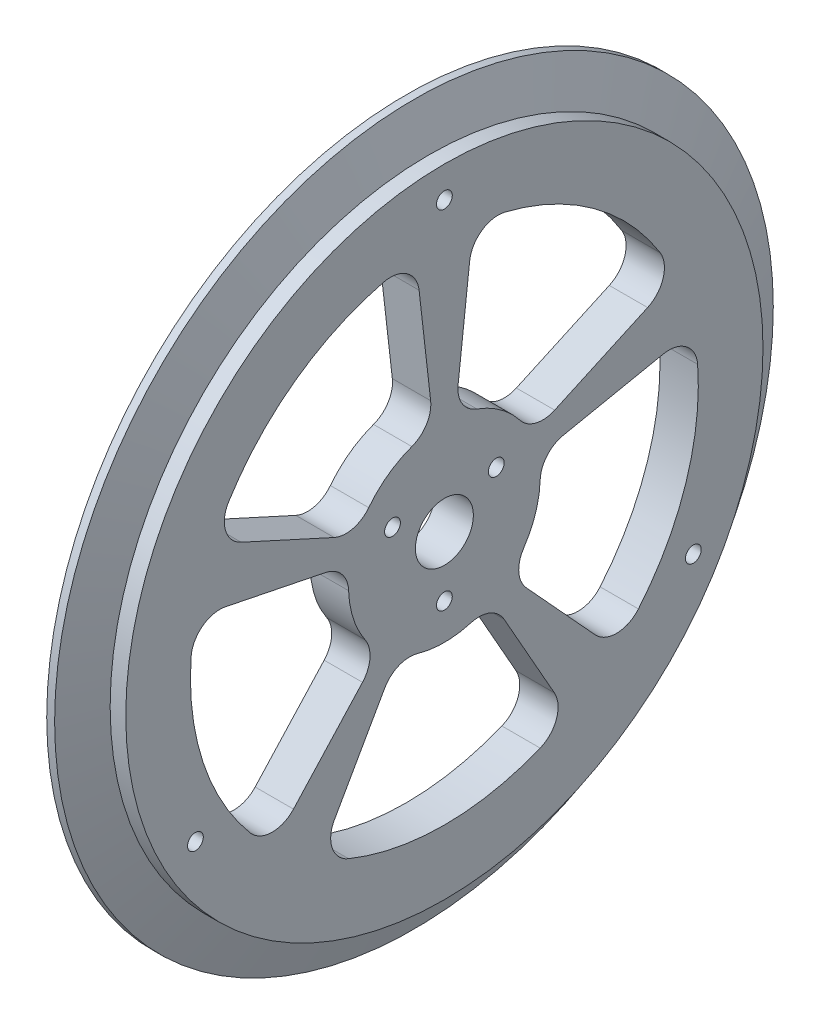
SolidWorks part; units mm, degrees
ref_plane "Front Plane" through (0, 0, 0) normal (0, 0, 1) x (1, 0, 0)
ref_plane "Top Plane" through (0, 0, 0) normal (0, 1, 0) x (1, 0, 0)
ref_plane "Right Plane" through (0, 0, 0) normal (1, 0, 0) x (0, 0, -1)
sketch "Sketch3" plane through (0, 0, 0) normal (0, 0, 1) x (1, 0, 0)
  line L1 (0, 0) -> (8, 0)
  line L2 (0, 0) -> (0, 75)
  line L3 (0, 75) -> (1.65, 75)
  line L5 (8, 120) -> (8, 104.2471) construction
  line L6 (8, 66.5) -> (4.7437, 66.5)
  line L8 (1.65, 75) -> (4.7437, 66.5)
  line L9 (8, 66.5) -> (8, 0)
  point P11 (8, 66.5)
  dimension "D1" = 8
  dimension "D2" = 75
  dimension "D3" = 6.35
  dimension "D4" = 20
  dimension "D5" = 8.5
  dimension "D6" = 1.65
revolve "Revolve1" add sketch "Sketch3" angle 360 about L1
ref_plane "Plane1" through (0, -36, 0) normal (0, 1, 0) x (1, 0, 0)
sketch "Sketch6" plane through (0, -36, 0) normal (0, 1, 0) x (1, 0, 0)
  line L0 (0, 75) -> (0, -75) construction
  line L1 (0, 2.5) -> (2, 2.5)
  line L2 (0, 2.5) -> (0, -2.5)
  line L3 (0, -2.5) -> (2, -2.5)
  line L4 (2, 2.5) -> (2, -2.5)
  line L5 (0, 0) -> (6.7273, 0) construction
  dimension "D1" = 5
  dimension "D2" = 2
extrude "Cut-Extrude2" [suppressed] cut sketch "Sketch6" against normal blind 65.4
sketch "Sketch5" plane through (0, 0, 0) normal (1, 0, 0) x (0, 0, -1)
  circle A0 centre (0, 0) radius 6.05
  dimension "D1" = 12.1
extrude "Cut-Extrude1" cut sketch "Sketch5" along normal through all
sketch "Sketch7" plane through (8, 0, 0) normal (1, 0, 0) x (0, 0, -1)
  line L0 (0, 0) -> (96.1964, -55.539) construction
  line L1 (0, 0) -> (0, 79.1103) construction
  line L2 (0, 0) -> (-91.2375, -52.676) construction
  line L3 (0, 0) -> (43.1357, 24.9044) construction
  line L4 (0, 0) -> (-44.6886, 25.801) construction
  line L5 (0, 0) -> (0, -35.7972) construction
  circle A0 centre (0, 0) radius 60 construction
  circle A1 centre (0, 60) radius 1.65
  circle A2 centre (51.9615, -30) radius 1.65
  circle A3 centre (-51.9615, -30) radius 1.65
  circle A4 centre (0, 0) radius 12.5 construction
  circle A5 centre (10.8253, 6.25) radius 1.65
  circle A6 centre (0, -12.5) radius 1.65
  circle A7 centre (-10.8253, 6.25) radius 1.65
  dimension "D3" = 120
  dimension "D4" = 3.3
  dimension "D5" = 3.3
  dimension "D6" = 3.3
  dimension "D7" = 25
  dimension "D10" = 3.3
  dimension "D11" = 3.3
  dimension "D12" = 3.3
  dimension "D1" = 120
  dimension "D2" = 120
  dimension "D8" = 60
  dimension "D9" = 60
extrude "Cut-Extrude3" cut sketch "Sketch7" against normal through all
sketch "Sketch8" plane through (8, 0, 0) normal (1, 0, 0) x (0, 0, -1)
  line L0 (2.2641, 19.8714) -> (5.9998, 52.6593)
  line L1 (0, 0) -> (98.161, 19.9711) construction
  line L2 (18.1992, 8.2939) -> (48.2279, 21.9787)
  line L3 (0, 0) -> (0, 85.1656) construction
  line L4 (0, 0) -> (18.1992, 8.2939) construction
  line L5 (0, 0) -> (10.8718, 95.4203) construction
  arc A0 (18.1992, 8.2939) -> (2.2641, 19.8714) centre (0, 0) ccw
  arc A1 (48.2279, 21.9787) -> (5.9998, 52.6593) centre (0, 0) ccw
  dimension "D1" = 40
  dimension "D2" = 106
  dimension "D3" = 72
  dimension "D4" = 13
  dimension "D5" = 6.5
extrude "Cut-Extrude4" cut sketch "Sketch8" against normal through all contours A1 L0 A0 L2
fillet "Fillet1" radius 6 4 edges at (4, 21.9787, -48.2279) (4, 52.6593, -5.9998) (4, 8.2939, -18.1992) (4, 19.8714, -2.2641)
ref_axis "Axis1" through (8, 0, 0) along (-1, 0, 0)
pattern_circular "CirPattern1" count 5 over 360 about axis through (8, 0, 0) along (-1, 0, 0) of "Cut-Extrude4", "Fillet1"
equation "\"D12@Sketch7\"=\"D4@Sketch7\""
equation "\"D11@Sketch7\"=\"D4@Sketch7\""
equation "\"D10@Sketch7\"=\"D4@Sketch7\""
equation "\"D6@Sketch7\"=\"D4@Sketch7\""
equation "\"D5@Sketch7\"=\"D4@Sketch7\""
